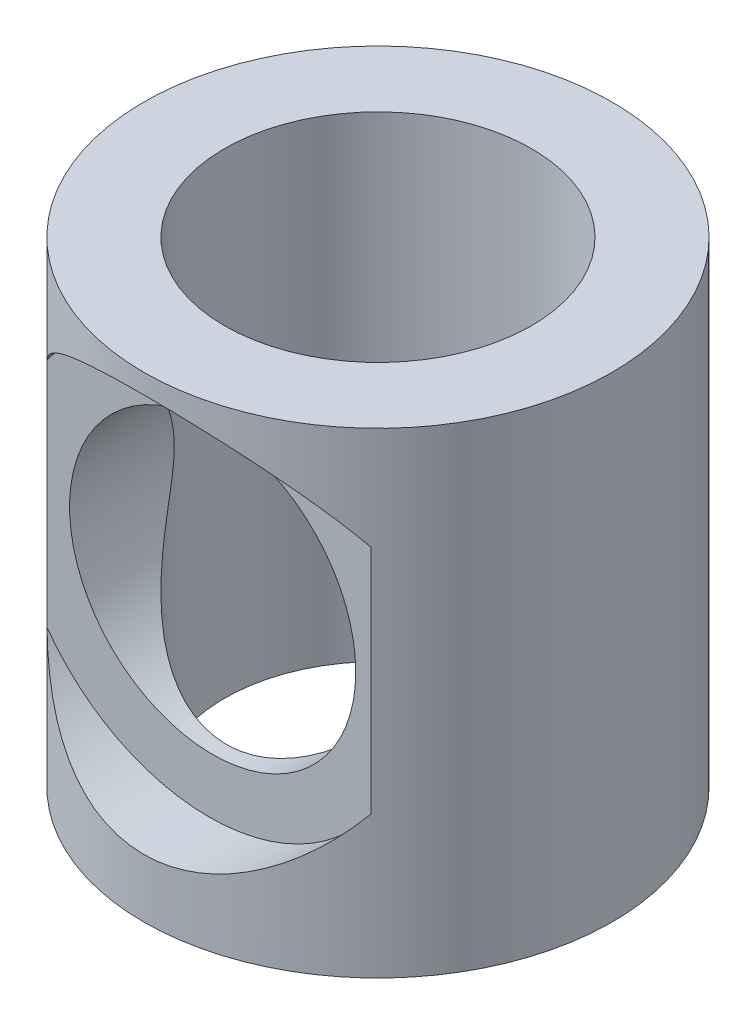
SolidWorks part; units mm, degrees
material "PTFE (general)"
ref_plane "Front Plane" through (0, 0, 0) normal (0, 0, 1) x (1, 0, 0)
ref_plane "Top Plane" through (0, 0, 0) normal (0, 1, 0) x (1, 0, 0)
ref_plane "Right Plane" through (0, 0, 0) normal (1, 0, 0) x (0, 0, -1)
sketch "Sketch1" plane through (0, 0, 0) normal (0, 1, 0) x (1, 0, 0)
  circle A0 centre (0, 0) radius 9
  circle A1 centre (0, 0) radius 5.9
  dimension "D1" = 18
  dimension "D2" = 11.8
extrude "Boss-Extrude1" add sketch "Sketch1" against normal blind 18.3
sketch "Sketch3" plane through (0, 0, 0) normal (0, 0, 1) x (1, 0, 0)
  line L1 (5.9, 0) -> (-5.9, 0) construction
  circle A0 centre (0, -8.4) radius 7.65
  dimension "D1" = 15.3
  dimension "D2" = 8.4
extrude "Cut-Extrude5" cut sketch "Sketch3" along normal through all from offset 6.5
sketch "Sketch6" plane through (0, 0, 6.5) normal (0, 0, 1) x (1, 0, 0)
  line L0 (-6.2249, -18.3) -> (6.2249, -18.3) construction
  line L1 (6.2249, 0) -> (6.2249, -18.3) construction
  circle A0 centre (0.1455, -8.4) radius 5.5
  dimension "D1" = 11
  dimension "D2" = 9.9
  dimension "D3" = 6.0795
extrude "Cut-Extrude6" cut sketch "Sketch6" against normal blind 7 and the other way through all
